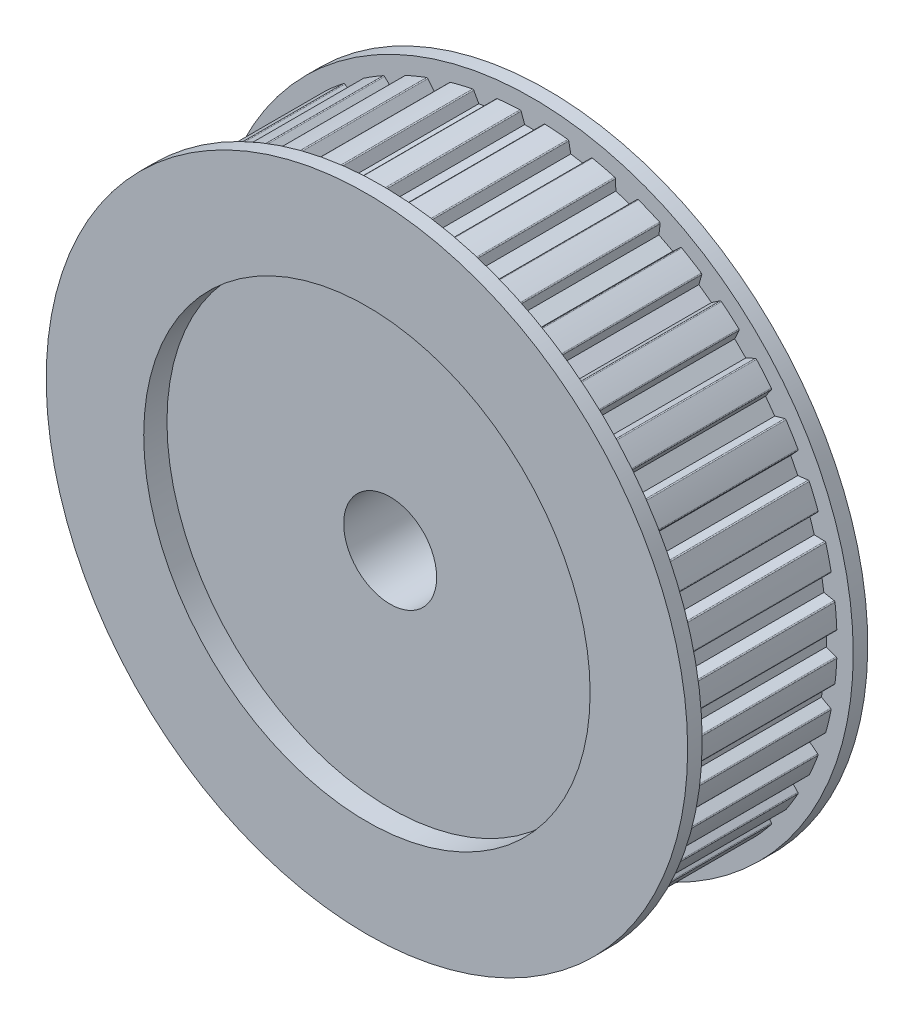
SolidWorks part; units mm, degrees
material "6061-T6 (SS)"
ref_plane "Front Plane" through (0, 0, 0) normal (0, 0, 1) x (1, 0, 0)
ref_plane "Top Plane" through (0, 0, 0) normal (0, 1, 0) x (1, 0, 0)
ref_plane "Right Plane" through (0, 0, 0) normal (1, 0, 0) x (0, 0, -1)
sketch "Sketch1" plane through (0, 0, 0) normal (0, 1, 0) x (1, 0, 0)
  line L0 (63.5, -10.3187) -> (0, -10.3187)
  line L1 (0, -10.3187) -> (0, -12.3031)
  line L2 (0, -12.3031) -> (63.5, -12.3031)
  line L3 (63.5, -12.3031) -> (63.5, -10.3187)
  line L4 (0, -10.3187) -> (0, -12.3031) construction
  dimension "D1" = 63.5
  dimension "D2" = 1.9844
revolve "Revolve1" add sketch "Sketch1" angle 360 about L4 reverse direction yes
sketch "Sketch2" plane through (0, 0, 10.3187) normal (0, 0, -1) x (-1, 0, 0)
  line L0 (20.8148, -56.5864) -> (19.4459, -54.8343)
  line L1 (19.4459, -54.8343) -> (16.4988, -55.7919)
  line L2 (16.4988, -55.7919) -> (16.4212, -58.014)
  line L3 (-25.2944, -54.7309) -> (-25.0234, -52.524)
  line L4 (-25.0234, -52.524) -> (-27.7845, -51.1172)
  line L5 (-27.7845, -51.1172) -> (-29.4106, -52.6336)
  line L6 (-52.6336, -29.4106) -> (-51.1172, -27.7845)
  line L7 (-51.1172, -27.7845) -> (-52.524, -25.0234)
  line L8 (-52.524, -25.0234) -> (-54.7309, -25.2944)
  line L9 (-58.014, 16.4212) -> (-55.7919, 16.4988)
  line L10 (-55.7919, 16.4988) -> (-54.8343, 19.4459)
  line L11 (-54.8343, 19.4459) -> (-56.5864, 20.8148)
  line L12 (-37.2822, 47.3848) -> (-35.4389, 46.1414)
  line L13 (-35.4389, 46.1414) -> (-32.9319, 47.9629)
  line L14 (-32.9319, 47.9629) -> (-33.5448, 50.1002)
  line L15 (7.1436, 59.8686) -> (7.5678, 57.686)
  line L16 (7.5678, 57.686) -> (10.6285, 57.2012)
  line L17 (10.6285, 57.2012) -> (11.7064, 59.1459)
  line L18 (40.9692, 44.2358) -> (40.0295, 42.2207)
  line L19 (40.0295, 42.2207) -> (42.2207, 40.0295)
  line L20 (42.2207, 40.0295) -> (44.2358, 40.9692)
  line L21 (59.1459, 11.7064) -> (57.2012, 10.6285)
  line L22 (57.2012, 10.6285) -> (57.686, 7.5678)
  line L23 (57.686, 7.5678) -> (59.8686, 7.1436)
  line L24 (50.1002, -33.5448) -> (47.9629, -32.9319)
  line L25 (47.9629, -32.9319) -> (46.1414, -35.4389)
  line L26 (46.1414, -35.4389) -> (47.3848, -37.2822)
  arc A0 (47.3848, -37.2822) -> (20.8148, -56.5864) centre (0, 0) cw
  arc A1 (16.4212, -58.014) -> (-25.2944, -54.7309) centre (0, 0) cw
  arc A2 (-29.4106, -52.6336) -> (-52.6336, -29.4106) centre (0, 0) cw
  arc A3 (-54.7309, -25.2944) -> (-58.014, 16.4212) centre (0, 0) cw
  arc A4 (-56.5864, 20.8148) -> (-37.2822, 47.3848) centre (0, 0) cw
  arc A5 (-33.5448, 50.1002) -> (7.1436, 59.8686) centre (0, 0) cw
  arc A6 (11.7064, 59.1459) -> (40.9692, 44.2358) centre (0, 0) cw
  arc A7 (44.2358, 40.9692) -> (59.1459, 11.7064) centre (0, 0) cw
  arc A8 (59.8686, 7.1436) -> (50.1002, -33.5448) centre (0, 0) cw
  circle A9 centre (0, 0) radius 63.5 construction
  dimension "D1" = 60.2933
  dimension "D2" = 60.2933
  dimension "D3" = 60.2933
  dimension "D4" = 60.2932
  dimension "D5" = 60.2933
  dimension "D6" = 60.2933
  dimension "D7" = 60.2932
  dimension "D8" = 60.2933
  dimension "D9" = 60.2933
  dimension "D10" = 7.1436
  dimension "D11" = 7.5678
  dimension "D12" = 10.6285
  dimension "D13" = 11.7064
  dimension "D14" = 16.4212
  dimension "D15" = 16.4988
  dimension "D16" = 19.4459
  dimension "D17" = 20.8148
  dimension "D18" = 40.0295
  dimension "D19" = 40.9692
  dimension "D20" = 42.2207
  dimension "D21" = 44.2358
  dimension "D22" = 46.1414
  dimension "D23" = 47.3848
  dimension "D24" = 47.9629
  dimension "D25" = 50.1002
  dimension "D26" = 57.2012
  dimension "D27" = 57.686
  dimension "D28" = 59.1459
  dimension "D29" = 59.8686
  dimension "D30" = 25.0234
  dimension "D31" = 25.2944
  dimension "D32" = 27.7845
  dimension "D33" = 29.4106
  dimension "D34" = 32.9319
  dimension "D35" = 33.5448
  dimension "D36" = 35.4389
  dimension "D37" = 37.2822
  dimension "D38" = 51.1172
  dimension "D39" = 52.524
  dimension "D40" = 52.6336
  dimension "D41" = 54.7309
  dimension "D42" = 54.8343
  dimension "D43" = 55.7919
  dimension "D44" = 56.5864
  dimension "D45" = 58.014
  dimension "D46" = 7.1436
  dimension "D47" = 7.5678
  dimension "D48" = 10.6285
  dimension "D49" = 11.7064
  dimension "D51" = 16.4988
  dimension "D52" = 19.4459
  dimension "D54" = 40.0295
  dimension "D56" = 42.2207
  dimension "D58" = 46.1414
  dimension "D60" = 47.9629
  dimension "D62" = 57.2012
  dimension "D63" = 57.686
  dimension "D66" = 25.0234
  dimension "D68" = 27.7845
  dimension "D70" = 32.9319
  dimension "D72" = 35.4389
  dimension "D74" = 51.1172
  dimension "D75" = 52.524
  dimension "D78" = 54.8343
  dimension "D79" = 55.7919
extrude "Boss-Extrude1" add sketch "Sketch2" along normal blind 20.6375
ref_plane "Plane1" through (0, 0, -10.3187) normal (0, 0, 1) x (1, 0, 0)
sketch "Sketch3" plane through (0, 0, -10.3187) normal (0, 0, 1) x (1, 0, 0)
  circle A0 centre (0, 0) radius 63.5
  dimension "D1" = 127
extrude "Boss-Extrude2" add sketch "Sketch3" against normal blind 1.9844
hole_wizard "Hole1" positions "Sketch5" profile "Sketch4" legacy
sketch "Sketch5" plane through (0, 0, -12.3031) normal (0, 0, -1) x (-1, 0, 0)
  point P0 (0, 0)
sketch "Sketch4" plane through (0, 0, -12.3031) normal (1, 0, 0) x (0, 1, 0)
  line L0 (0, 0) -> (0, 9.9219)
  line L1 (0, 9.9219) -> (44.1912, 9.9219)
  line L2 (44.1912, 9.9219) -> (44.1912, 0)
  line L3 (44.1912, 0) -> (0, 0)
  line L4 (0, 110) -> (0, -10) construction
  dimension "Diameter" = 88.3825
  dimension "Depth" = 9.9219
hole_wizard "Hole2" positions "Sketch7" profile "Sketch6" legacy
sketch "Sketch7" plane through (0, 0, 12.3031) normal (0, 0, 1) x (1, 0, 0)
  point P0 (0, 0)
sketch "Sketch6" plane through (0, 0, 12.3031) normal (1, 0, 0) x (0, -1, 0)
  line L0 (0, 0) -> (0, 9.9219)
  line L1 (0, 9.9219) -> (44.1912, 9.9219)
  line L2 (44.1912, 9.9219) -> (44.1912, 0)
  line L3 (44.1912, 0) -> (0, 0)
  line L4 (0, 110) -> (0, -10) construction
  dimension "Diameter" = 88.3825
  dimension "Depth" = 9.9219
fillet "Fillet1" radius 0.2286 18 edges at (-7.1436, 59.8686, 0) (58.014, 16.4212, 0) (52.6336, -29.4106, 0) (-59.1459, 11.7064, 0) (37.2822, 47.3848, 0) (-59.8686, 7.1436, 0) (-44.2358, 40.9692, 0) (-50.1002, -33.5448, 0) (54.7309, -25.2944, 0) (-47.3848, -37.2822, 0) (56.5864, 20.8148, 0) (-20.8148, -56.5864, 0) (33.5448, 50.1002, 0) (-16.4212, -58.014, 0) (-11.7064, 59.1459, 0) (25.2944, -54.7309, 0) (-40.9692, 44.2358, 0) (29.4106, -52.6336, 0) tangent propagation no
sketch "Sketch12" plane through (0, 0, -10.3187) normal (0, 0, 1) x (1, 0, 0)
  line L0 (35.4389, 46.1414) -> (37.1438, 47.2914) construction
  line L1 (32.9319, 47.9629) -> (35.4389, 46.1414) construction
  line L2 (33.4987, 49.9397) -> (32.9319, 47.9629) construction
  line L3 (35.4389, 46.1414) -> (37.1438, 47.2914)
  line L4 (32.9319, 47.9629) -> (35.4389, 46.1414)
  line L5 (33.4987, 49.9397) -> (32.9319, 47.9629)
  arc A0 (37.4135, 47.2812) -> (37.1438, 47.2914) centre (37.2716, 47.1019) ccw construction
  arc A1 (33.4987, 49.9397) -> (33.4057, 50.193) centre (33.279, 50.0027) ccw construction
  arc A2 (37.4135, 47.2812) -> (37.1438, 47.2914) centre (37.2716, 47.1019) ccw
  arc A3 (33.4987, 49.9397) -> (33.4057, 50.193) centre (33.279, 50.0027) ccw
  arc A4 (33.4057, 50.193) -> (37.4135, 47.2812) centre (0.056, 0.0771) cw
  dimension "D1" = 60.198
extrude "Cut-Extrude1" cut sketch "Sketch12" along normal blind 20.6502
pattern_circular "CirPattern2" count 40 over 360 about axis through (0, 0, 12.3031) along (0, 0, 1) of "Cut-Extrude1"
scale "Scale1" bodies to scale 112 scale about origin uniform scaling no x scale factor 2.3 y scale factor 2.3 z scale factor 1
sketch "Sketch13" plane through (0, 0, 0) normal (0, 0, 1) x (1, 0, 0)
  circle A0 centre (0, 0) radius 6.35
  dimension "D1" = 12.7
extrude "Cut-Extrude2" cut sketch "Sketch13" against normal through all both and the other way through all
scale "Scale2" bodies to scale 114 scale about origin uniform scaling no x scale factor 0.3 y scale factor 0.3 z scale factor 1
sketch "Sketch14" plane through (0, 0, 12.3031) normal (0, 0, 1) x (1, 0, 0)
  circle A0 centre (0, 0) radius 30.492 construction
  circle A1 centre (0, 0) radius 30.492
extrude "Boss-Extrude3" add sketch "Sketch14" against normal offset from surface (18.2563 mm away) 3.175 from offset 3.175 up to face at (-30.492, 0, -12.3031) offset against normal yes
sketch "Sketch15" plane through (0, 0, 12.3031) normal (0, 0, 1) x (1, 0, 0)
  circle A0 centre (0, 0) radius 6.35
  dimension "D1" = 12.7
extrude "Cut-Extrude3" cut sketch "Sketch15" against normal through all
equation "\"0.8125in.\"=0.813"
equation "\"D1@Cut-Extrude1\"=\"0.8125in.\""
